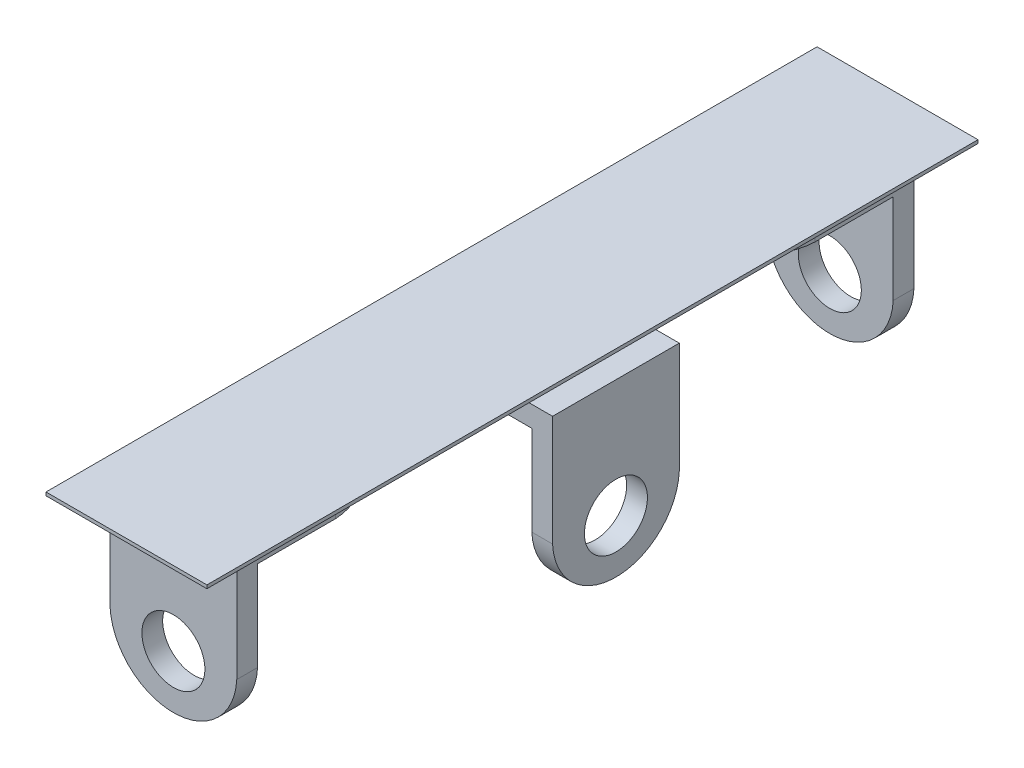
SolidWorks part; units mm, degrees
ref_plane "Front Plane" through (0, 0, 0) normal (0, 0, 1) x (1, 0, 0)
ref_plane "Top Plane" through (0, 0, 0) normal (0, 1, 0) x (1, 0, 0)
ref_plane "Right Plane" through (0, 0, 0) normal (1, 0, 0) x (0, 0, -1)
ref_plane "Plane1" through (0, 0, 0) normal (0, 1, 0) x (1, 0, 0)
sketch "Sketch1" plane through (0, 0, 0) normal (0, 1, 0) x (1, 0, 0)
  line L0 (-3.048, -14.605) -> (3.048, -14.605)
  line L1 (3.048, -14.605) -> (3.048, 14.605)
  line L2 (3.048, 14.605) -> (-3.048, 14.605)
  line L3 (-3.048, 14.605) -> (-3.048, -14.605)
extrude "Boss-Extrude1" add sketch "Sketch1" along normal blind 0.127
ref_plane "Plane2" through (0, 0, 0) normal (0, 1, 0) x (1, 0, 0)
sketch "Sketch2" plane through (0, 0, 0) normal (0, 1, 0) x (1, 0, 0)
  line L0 (-0.1172, -2.4003) -> (3.5404, -2.4003)
  line L1 (3.5404, -2.4003) -> (3.5404, 2.4003)
  line L2 (3.5404, 2.4003) -> (-0.1172, 2.4003)
  arc A0 (-0.1172, 2.4003) -> (-0.1172, -2.4003) centre (0, 0) ccw
extrude "Boss-Extrude2" add sketch "Sketch2" against normal blind 0.7874
ref_plane "Plane3" through (0, 0, 0) normal (0, 1, 0) x (1, 0, 0)
sketch "Sketch3" plane through (0, 0, 0) normal (0, 1, 0) x (1, 0, 0)
  line L0 (2.4003, 9.0776) -> (2.4003, 12.7352)
  line L1 (2.4003, 12.7352) -> (-2.4003, 12.7352)
  line L2 (-2.4003, 12.7352) -> (-2.4003, 9.0776)
  arc A0 (-2.4003, 9.0776) -> (2.4003, 9.0776) centre (0, 9.1948) ccw
extrude "Boss-Extrude3" add sketch "Sketch3" against normal blind 0.7874
ref_plane "Plane4" through (0, 0, 0) normal (0, 1, 0) x (1, 0, 0)
sketch "Sketch4" plane through (0, 0, 0) normal (0, 1, 0) x (1, 0, 0)
  line L0 (-2.4003, -12.7352) -> (2.4003, -12.7352)
  line L1 (2.4003, -12.7352) -> (2.4003, -9.0776)
  line L2 (-2.4003, -9.0776) -> (-2.4003, -12.7352)
  arc A0 (2.4003, -9.0776) -> (-2.4003, -9.0776) centre (0, -9.1948) ccw
extrude "Boss-Extrude4" add sketch "Sketch4" against normal blind 0.7874
ref_plane "Plane5" through (3.937, 0, 0) normal (1, 0, 0) x (0, 0, -1)
sketch "Sketch5" plane through (3.937, 0, 0) normal (1, 0, 0) x (0, 0, -1)
  line L0 (-2.4003, 0) -> (-2.4003, -4.191)
  line L1 (2.4003, -4.191) -> (2.4003, 0)
  line L2 (2.4003, 0) -> (-2.4003, 0)
  arc A0 (-2.4003, -4.191) -> (2.4003, -4.191) centre (0, -4.0738) ccw
  circle A1 centre (0, -4.4577) radius 1.1938
extrude "Boss-Extrude5" add sketch "Sketch5" against normal blind 0.7874
ref_plane "Plane6" through (0, 0, 12.827) normal (0, 0, 1) x (1, 0, 0)
sketch "Sketch6" plane through (0, 0, 12.827) normal (0, 0, 1) x (1, 0, 0)
  line L0 (-2.4003, 0) -> (-2.4003, -4.191)
  line L1 (2.4003, -4.191) -> (2.4003, 0)
  line L2 (2.4003, 0) -> (-2.4003, 0)
  arc A0 (-2.4003, -4.191) -> (2.4003, -4.191) centre (0, -4.0738) ccw
  circle A1 centre (0, -4.4577) radius 1.1938
extrude "Boss-Extrude6" add sketch "Sketch6" against normal blind 0.7874
ref_plane "Plane7" through (0, 0, -12.827) normal (0, 0, 1) x (1, 0, 0)
sketch "Sketch7" plane through (0, 0, -12.827) normal (0, 0, 1) x (1, 0, 0)
  line L0 (-2.4003, 0) -> (-2.4003, -4.191)
  line L1 (2.4003, -4.191) -> (2.4003, 0)
  line L2 (2.4003, 0) -> (-2.4003, 0)
  arc A0 (-2.4003, -4.191) -> (2.4003, -4.191) centre (0, -4.0738) ccw
  circle A1 centre (0, -4.4577) radius 1.1938
extrude "Boss-Extrude7" add sketch "Sketch7" along normal blind 0.7874
ref_plane "Plane8" through (0, 0, 0) normal (0, 0, 1) x (1, 0, 0)
sketch "Sketch8" plane through (0, 0, 0) normal (0, 0, 1) x (1, 0, 0)
  line L0 (0, 0) -> (1.651, 0)
  line L1 (1.651, 0) -> (1.651, -0.7874)
  line L2 (0, -1.3462) -> (0, 0)
  line L3 (0, -1.3462) -> (0, 0) construction
  arc A0 (1.651, -0.7874) -> (0, -1.3462) centre (0, 1.3722) cw
revolve "Revolve1" add sketch "Sketch8" angle 360 about L3 reverse direction yes
ref_plane "Plane9" through (0, 0, 0) normal (1, 0, 0) x (0, 0, -1)
sketch "Sketch9" plane through (0, 0, 0) normal (1, 0, 0) x (0, 0, -1)
  line L0 (9.1948, 0) -> (10.8458, 0)
  line L1 (10.8458, 0) -> (10.8458, -0.7874)
  line L2 (9.1948, -1.3462) -> (9.1948, 0)
  line L3 (9.1948, -1.3462) -> (9.1948, 0) construction
  arc A0 (10.8458, -0.7874) -> (9.1948, -1.3462) centre (9.1948, 1.3722) cw
revolve "Revolve2" add sketch "Sketch9" angle 360 about L3 reverse direction yes
ref_plane "Plane10" through (0, 0, 0) normal (1, 0, 0) x (0, 0, -1)
sketch "Sketch10" plane through (0, 0, 0) normal (1, 0, 0) x (0, 0, -1)
  line L0 (-9.1948, 0) -> (-7.5438, 0)
  line L1 (-7.5438, 0) -> (-7.5438, -0.7874)
  line L2 (-9.1948, -1.3462) -> (-9.1948, 0)
  line L3 (-9.1948, -1.3462) -> (-9.1948, 0) construction
  arc A0 (-7.5438, -0.7874) -> (-9.1948, -1.3462) centre (-9.1948, 1.3722) cw
revolve "Revolve3" add sketch "Sketch10" angle 360 about L3 reverse direction yes
other "PIN 1" parameters "Diameter"=0.8128, "StubLength"=0
ref_axis "Axis2" through (0, -4.4577, -22.0396) along (0, 0, 1)
other "PIN 2" parameters "Diameter"=0.8128, "StubLength"=0
ref_axis "Axis3" through (13.1496, -4.4577, 0) along (-1, 0, 0)
other "PIN 3" parameters "Diameter"=0.8128, "StubLength"=0
ref_axis "Axis4" through (0, -4.4577, 22.0396) along (0, 0, -1)
